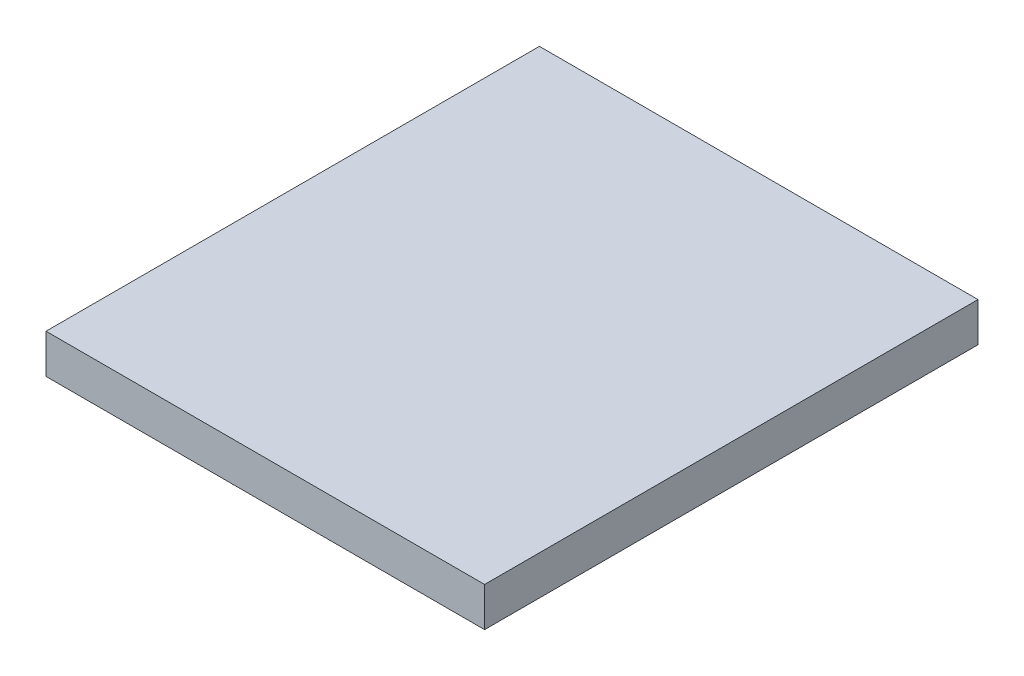
SolidWorks part; units mm, degrees
material "Polyurethane Foam Flexible"
ref_plane "Front Plane" through (0, 0, 0) normal (0, 0, 1) x (1, 0, 0)
ref_plane "Top Plane" through (0, 0, 0) normal (0, 1, 0) x (1, 0, 0)
ref_plane "Right Plane" through (0, 0, 0) normal (1, 0, 0) x (0, 0, -1)
sketch "Sketch1" plane through (0, 0, 0) normal (0, 1, 0) x (1, 0, 0)
  line L1 (0, 0) -> (355.6, 0)
  line L2 (0, 0) -> (0, 400.05)
  line L3 (0, 400.05) -> (355.6, 400.05)
  line L4 (355.6, 0) -> (355.6, 400.05)
  dimension "D1" = 355.6
  dimension "D2" = 400.05
extrude "Boss-Extrude1" add sketch "Sketch1" along normal blind 31.75
